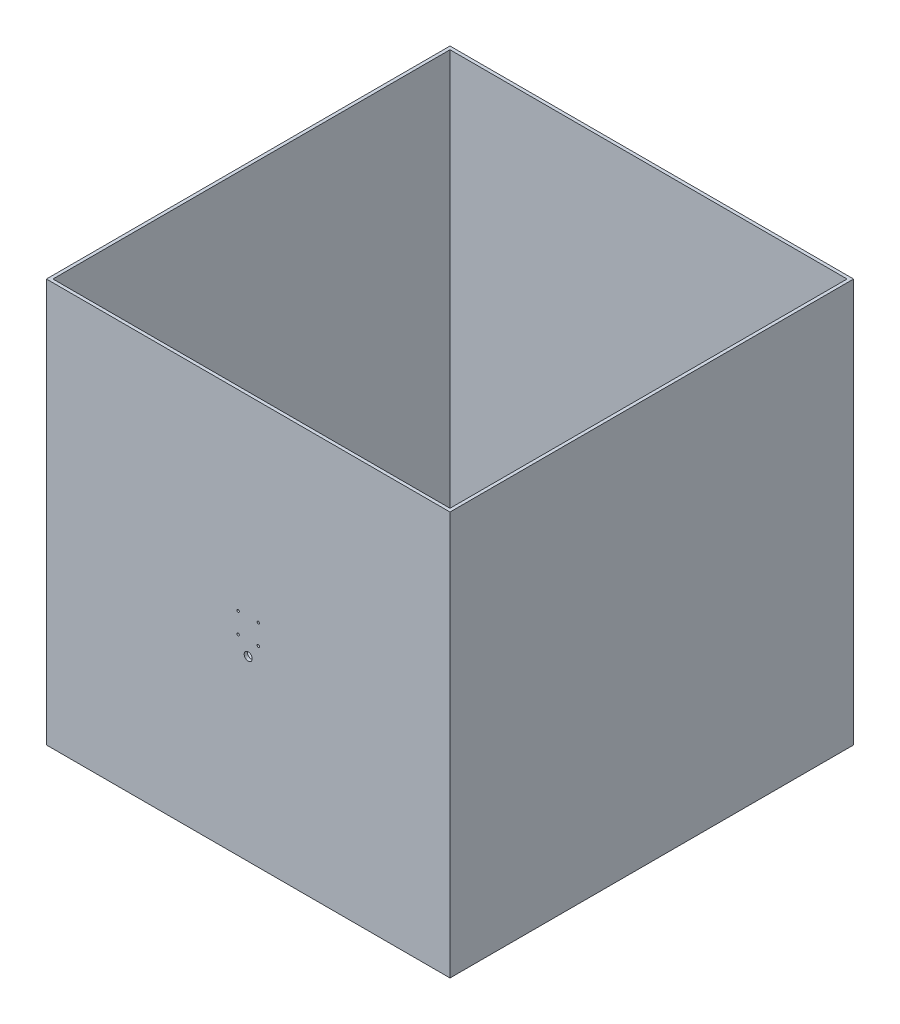
SolidWorks part; units mm, degrees
material "Perspex (TM) GS Acrylic Cast Sheet"
ref_plane "Front Plane" through (0, 0, 0) normal (0, 0, 1) x (1, 0, 0)
ref_plane "Top Plane" through (0, 0, 0) normal (0, 1, 0) x (1, 0, 0)
ref_plane "Right Plane" through (0, 0, 0) normal (1, 0, 0) x (0, 0, -1)
sketch "Sketch1" plane through (0, 0, 0) normal (0, 1, 0) x (1, 0, 0)
  line L1 (-250, -250) -> (250, -250)
  line L2 (-250, -250) -> (-250, 250)
  line L3 (-250, 250) -> (250, 250)
  line L4 (250, -250) -> (250, 250)
  line L5 (-250, -250) -> (250, 250) construction
  line L6 (-250, 250) -> (250, -250) construction
  point P0 (0, 0)
  dimension "D1" = 500
  dimension "D2" = 500
extrude "Boss-Extrude1" add sketch "Sketch1" along normal blind 500
shell "Shell1" thickness 4 removed face at (0, 500, 0)
sketch "Sketch2" plane through (0, 0, 250) normal (0, 0, 1) x (1, 0, 0)
  line L0 (0, -275) -> (0, 275) construction
  line L1 (-12.5, 237.5) -> (12.5, 237.5) construction
  line L2 (-12.5, 237.5) -> (-12.5, 262.5) construction
  line L3 (-12.5, 262.5) -> (12.5, 262.5) construction
  line L4 (12.5, 237.5) -> (12.5, 262.5) construction
  line L5 (-12.5, 237.5) -> (12.5, 262.5) construction
  line L6 (-12.5, 262.5) -> (12.5, 237.5) construction
  line L7 (-250, 500) -> (250, 500) construction
  circle A0 centre (-12.5, 262.5) radius 1.5
  circle A1 centre (12.5, 262.5) radius 1.5
  circle A2 centre (12.5, 237.5) radius 1.5
  circle A3 centre (-12.5, 237.5) radius 1.5
  circle A4 centre (0, 220) radius 5
  point P0 (0, 250)
  dimension "D4" = 3
  dimension "D5" = 10
  dimension "D1" = 25
  dimension "D2" = 25
  dimension "D3" = 250
  dimension "D6" = 30
extrude "Cut-Extrude1" cut sketch "Sketch2" against normal up to next
